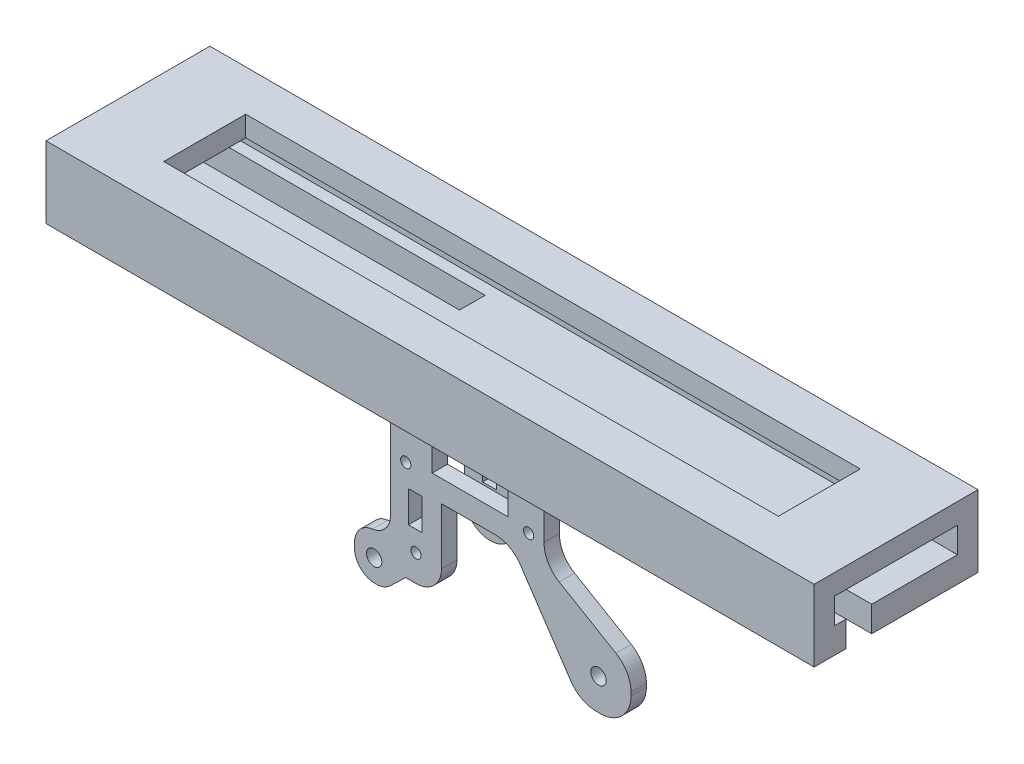
SolidWorks part; units mm, degrees
ref_plane "Front Plane" through (0, 0, 0) normal (0, 0, 1) x (1, 0, 0)
ref_plane "Top Plane" through (0, 0, 0) normal (0, 1, 0) x (1, 0, 0)
ref_plane "Right Plane" through (0, 0, 0) normal (1, 0, 0) x (0, 0, -1)
sketch "Sketch1" plane through (0, 0, 0) normal (0, 1, 0) x (1, 0, 0)
  line L1 (0, 0) -> (150, 0)
  line L2 (0, 0) -> (0, -32)
  line L3 (0, -32) -> (150, -32)
  line L4 (150, 0) -> (150, -32)
  dimension "D1" = 32
  dimension "D2" = 150
extrude "Boss-Extrude1" add sketch "Sketch1" along normal blind 5
sketch "Sketch2" plane through (0, 5, 0) normal (0, 1, 0) x (1, 0, 0)
  line L0 (150, -32) -> (150, 0) construction
  line L1 (0, -32) -> (150, -32)
  line L2 (0, -32) -> (0, -28)
  line L3 (0, -28) -> (150, -28)
  line L4 (150, -32) -> (150, -28)
  line L5 (0, 0) -> (0, -32) construction
  line L6 (150, 0) -> (0, 0)
  line L7 (150, 0) -> (150, -4)
  line L8 (150, -4) -> (0, -4)
  line L9 (0, 0) -> (0, -4)
  dimension "D1" = 4
  dimension "D2" = 4
extrude "Boss-Extrude2" add sketch "Sketch2" along normal blind 9
sketch "Sketch4" plane through (0, 0, 0) normal (-1, 0, 0) x (0, 0, 1)
  line L1 (4, 14) -> (8, 14)
  line L2 (4, 14) -> (4, 10)
  line L3 (4, 10) -> (8, 10)
  line L4 (8, 14) -> (8, 10)
  line L5 (28, 14) -> (24, 14)
  line L6 (28, 14) -> (28, 10)
  line L7 (28, 10) -> (24, 10)
  line L8 (24, 14) -> (24, 10)
  dimension "D1" = 4
  dimension "D2" = 4
  dimension "D3" = 4
  dimension "D4" = 4
extrude "Boss-Extrude3" add sketch "Sketch4" against normal blind 150
sketch "Sketch5" plane through (0, 0, 0) normal (0, -1, 0) x (-1, 0, 0)
  line L0 (-150, -32) -> (-150, 0) construction
  line L1 (-150, -20.75) -> (-90, -20.75)
  line L2 (-150, -20.75) -> (-150, -25.75)
  line L3 (-150, -25.75) -> (-90, -25.75)
  line L4 (-90, -20.75) -> (-90, -25.75)
  dimension "D1" = 5
  dimension "D2" = 20.75
  dimension "D3" = 60
extrude "Cut-Extrude1" cut sketch "Sketch5" against normal blind 6
sketch "Sketch6" plane through (0, 0, 24) normal (0, 0, -1) x (-1, 0, 0)
  line L0 (-150, 14) -> (-150, 10) construction
  line L1 (-150, 14) -> (-135, 14)
  line L2 (-150, 14) -> (-150, 10)
  line L3 (-150, 10) -> (-135, 10)
  line L4 (-135, 14) -> (-135, 10)
  line L5 (-150, 14) -> (0, 14) construction
  line L6 (-150, 10) -> (0, 10) construction
  line L7 (-75, 14) -> (-75, 10.8709) construction
  line L8 (-15, 14) -> (-15, 10)
  line L9 (0, 10) -> (-15, 10)
  line L10 (0, 14) -> (0, 10)
  line L11 (0, 14) -> (-15, 14)
  dimension "D1" = 15
extrude "Boss-Extrude4" add sketch "Sketch6" along normal up to next
sketch "Sketch7" plane through (0, 0, 0) normal (0, -1, 0) x (-1, 0, 0)
  line L0 (0, 0) -> (0, -32) construction
  line L1 (0, -11.25) -> (-60, -11.25)
  line L2 (0, -11.25) -> (0, -6.25)
  line L3 (0, -6.25) -> (-60, -6.25)
  line L4 (-60, -11.25) -> (-60, -6.25)
  line L5 (0, -32) -> (-150, -32) construction
  dimension "D1" = 60
  dimension "D2" = 5
  dimension "D3" = 20.75
extrude "Cut-Extrude2" cut sketch "Sketch7" against normal blind 6
sketch "Sketch8" plane through (0, 0, 0) normal (0, -1, 0) x (1, 0, 0)
  line L0 (0, 32) -> (150, 32) construction
  line L1 (90, 21.75) -> (60, 21.75)
  line L2 (90, 21.75) -> (90, 24.75)
  line L3 (90, 24.75) -> (60, 24.75)
  line L4 (60, 21.75) -> (60, 24.75)
  line L5 (0, 16) -> (20.6483, 16) construction
  line L6 (0, 11.25) -> (0, 32) construction
  line L7 (60, 10.25) -> (60, 7.25)
  line L8 (90, 10.25) -> (90, 7.25)
  line L9 (90, 10.25) -> (60, 10.25)
  line L10 (90, 7.25) -> (60, 7.25)
  point P4 (75, 24.75)
  point P7 (75, 32)
  dimension "D2" = 30
  dimension "D4" = 1
  dimension "D5" = 16
extrude "Boss-Extrude5" add sketch "Sketch8" along normal blind 16
sketch "Sketch9" plane through (0, 0, 7.25) normal (0, 0, -1) x (-1, 0, 0)
  line L0 (-60, 0) -> (-90, 0) construction
  line L1 (-90, -16) -> (-90, 0) construction
  circle A0 centre (-63, -12.5) radius 1
  circle A1 centre (-87, -12.5) radius 1
  dimension "D5" = 2
  dimension "D6" = 2
  dimension "D1" = 24
  dimension "D2" = 12.5
  dimension "D3" = 12.5
  dimension "D4" = 3
extrude "Cut-Extrude3" cut sketch "Sketch9" against normal through all
sketch "Sketch11" plane through (0, -16, 0) normal (0, -1, 0) x (-1, 0, 0)
  line L0 (-60, -7.25) -> (-90, -7.25) construction
  line L1 (-60, -10.25) -> (-70, -10.25)
  line L2 (-60, -10.25) -> (-60, -7.25)
  line L3 (-60, -7.25) -> (-70, -7.25)
  line L4 (-70, -10.25) -> (-70, -7.25)
  line L5 (-60, -21.75) -> (-90, -21.75) construction
  line L6 (-60, -24.75) -> (-70, -24.75)
  line L7 (-60, -24.75) -> (-60, -21.75)
  line L8 (-60, -21.75) -> (-70, -21.75)
  line L9 (-70, -24.75) -> (-70, -21.75)
  dimension "D1" = 10
  dimension "D2" = 10
extrude "Boss-Extrude7" add sketch "Sketch11" along normal blind 16
sketch "Sketch12" plane through (0, 0, 24.75) normal (0, 0, 1) x (1, 0, 0)
  line L0 (70, -32) -> (60, -32) construction
  line L1 (70, -32) -> (70, -16) construction
  circle A0 centre (65, -26.8) radius 1
  dimension "D1" = 2
  dimension "D2" = 5.2
  dimension "D3" = 5
extrude "Cut-Extrude4" cut sketch "Sketch12" against normal through all
sketch "Sketch13" plane through (0, -16, 0) normal (0, -1, 0) x (-1, 0, 0)
  line L0 (-90, -24.75) -> (-70, -24.75) construction
  line L1 (-87, -24.75) -> (-107, -24.75)
  line L2 (-87, -24.75) -> (-87, -21.75)
  line L3 (-87, -21.75) -> (-107, -21.75)
  line L4 (-107, -24.75) -> (-107, -21.75)
  line L5 (-70, -21.75) -> (-90, -21.75) construction
  line L6 (-90, -21.75) -> (-90, -24.75) construction
  dimension "D1" = 20
  dimension "D2" = 3
extrude "Boss-Extrude8" add sketch "Sketch13" along normal blind 20
sketch "Sketch14" plane through (0, -32, 0) normal (0, -1, 0) x (-1, 0, 0)
  line L0 (-60, -21.75) -> (-70, -21.75) construction
  line L1 (-63, -21.75) -> (-53, -21.75)
  line L2 (-63, -21.75) -> (-63, -24.75)
  line L3 (-63, -24.75) -> (-53, -24.75)
  line L4 (-53, -21.75) -> (-53, -24.75)
  line L5 (-70, -24.75) -> (-60, -24.75) construction
  dimension "D1" = 10
  dimension "D2" = 3
extrude "Boss-Extrude9" add sketch "Sketch14" along normal blind 4
sketch "Sketch15" plane through (0, -32, 0) normal (0, 1, 0) x (1, 0, 0)
  line L1 (60, -24.75) -> (53, -24.75)
  line L2 (60, -24.75) -> (60, -21.75)
  line L3 (60, -21.75) -> (53, -21.75)
  line L4 (53, -24.75) -> (53, -21.75)
extrude "Boss-Extrude10" add sketch "Sketch15" along normal blind 5
sketch "Sketch16" plane through (0, 0, 24.75) normal (0, 0, 1) x (1, 0, 0)
  circle A0 centre (56.83, -31.7075) radius 1.5
  circle A1 centre (100.6407, -29.8517) radius 1.5
  dimension "D1" = 3
  dimension "D2" = 3
extrude "Cut-Extrude5" cut sketch "Sketch16" against normal through all
sketch "Sketch17" plane through (0, 0, 24.75) normal (0, 0, 1) x (1, 0, 0)
  line L0 (97, -36) -> (87, -21.0569)
  line L1 (107, -36) -> (87, -36) construction
  line L2 (87, -36) -> (87, -16) construction
  line L3 (87, -21.0569) -> (87, -36)
  line L4 (87, -36) -> (97, -36)
extrude "Cut-Extrude6" cut sketch "Sketch17" against normal blind 5
sketch "Sketch18" plane through (0, 0, 24.75) normal (0, 0, 1) x (1, 0, 0)
  line L0 (107, -26) -> (90, -16)
  line L1 (107, -36) -> (107, -16) construction
  line L2 (90, -16) -> (107, -16)
  line L3 (107, -16) -> (107, -26)
extrude "Cut-Extrude7" cut sketch "Sketch18" against normal blind 5
sketch "Sketch19" plane through (0, 0, 24.75) normal (0, 0, 1) x (1, 0, 0)
  line L0 (87, -21.0569) -> (83.6159, -16)
  line L1 (87, -16) -> (70, -16) construction
  line L2 (83.6159, -16) -> (87, -16)
  line L3 (87, -21.0569) -> (87, -16) construction
  line L4 (87, -16) -> (87, -21.0569)
extrude "Boss-Extrude11" add sketch "Sketch19" against normal blind 3
sketch "Sketch20" plane through (0, 0, 24.75) normal (0, 0, 1) x (1, 0, 0)
  line L0 (58.8222, -36) -> (63, -32)
  line L1 (63, -36) -> (53, -36) construction
  line L2 (63, -32) -> (63, -36)
  line L3 (63, -36) -> (58.8222, -36)
extrude "Cut-Extrude8" cut sketch "Sketch20" against normal blind 3
sketch "Sketch21" plane through (0, 0, 7.25) normal (0, 0, -1) x (-1, 0, 0)
  line L1 (-68.1482, -11.738) -> (-82.9955, -11.738)
  line L2 (-68.1482, -11.738) -> (-68.1482, -3.4687)
  line L3 (-68.1482, -3.4687) -> (-82.9955, -3.4687)
  line L4 (-82.9955, -11.738) -> (-82.9955, -3.4687)
extrude "Cut-Extrude9" cut sketch "Sketch21" against normal through all
fillet "Fillet3" radius 6 3 edges at (107, -26, 23.25) (107, -36, 23.25) (97, -36, 23.25)
fillet "Fillet4" radius 4 3 edges at (58.8222, -36, 23.25) (53, -27, 23.25) (53, -36, 23.25)
fillet "Fillet5" radius 5 3 edges at (90, -16, 8.75) (70, -32, 8.75) (60, -32, 8.75)
fillet "Fillet6" radius 5 1 edges at (70, -32, 23.25)
sketch "Sketch22" plane through (0, 0, 7.25) normal (0, 0, -1) x (-1, 0, 0)
  line L1 (-63.5161, -16.6771) -> (-66.2025, -16.6771)
  line L2 (-63.5161, -16.6771) -> (-63.5161, -22.8124)
  line L3 (-63.5161, -22.8124) -> (-66.2025, -22.8124)
  line L4 (-66.2025, -16.6771) -> (-66.2025, -22.8124)
extrude "Cut-Extrude10" cut sketch "Sketch22" against normal through all
fillet "Fillet7" radius 6 1 edges at (90, -16, 23.25)
fillet "Fillet8" radius 6 1 edges at (83.6159, -16, 23.25)
fillet "Fillet9" radius 4 1 edges at (60, -27, 23.25)
fillet "Fillet10" radius 1 1 edges at (75, 0, 7.25)
fillet "Fillet11" radius 1 1 edges at (75, 0, 24.75)
equation "\"D1@Sketch1\"=15+1+4*4"
equation "\"D1@Boss-Extrude2\"=9"
equation "\"D1@Sketch7\"=\"D3@Sketch5\""
equation "\"D2@Sketch7\"=\"D1@Sketch5\""
equation "\"D3@Sketch7\"=\"D2@Sketch5\""
equation "\"D5@Sketch8\"=\"D1@Sketch1\"/2"
equation "\"D6@Sketch9\"=\"D5@Sketch9\""
equation "\"D2@Sketch9\"=\"D3@Sketch9\""
equation "\"D2@Sketch11\"=\"D1@Sketch11\""
equation "\"滑动-垂直孔\" = 0.6"
equation "\"滑动-水平孔\" = 0.3"
equation "\"松动-垂直孔\" = 0.3"
equation "\"松动-水平孔\" = 0.1"
equation "\"正常-垂直孔\" = 0.15"
equation "\"正常-水平孔\" = 0"
equation "\"紧缩-垂直孔\" = 0"
equation "\"紧缩-水平孔\" = -0.1"
equation "\"喷嘴宽度\" = \"_喷嘴物理宽度\" * \"_喷嘴宽度系数\""
